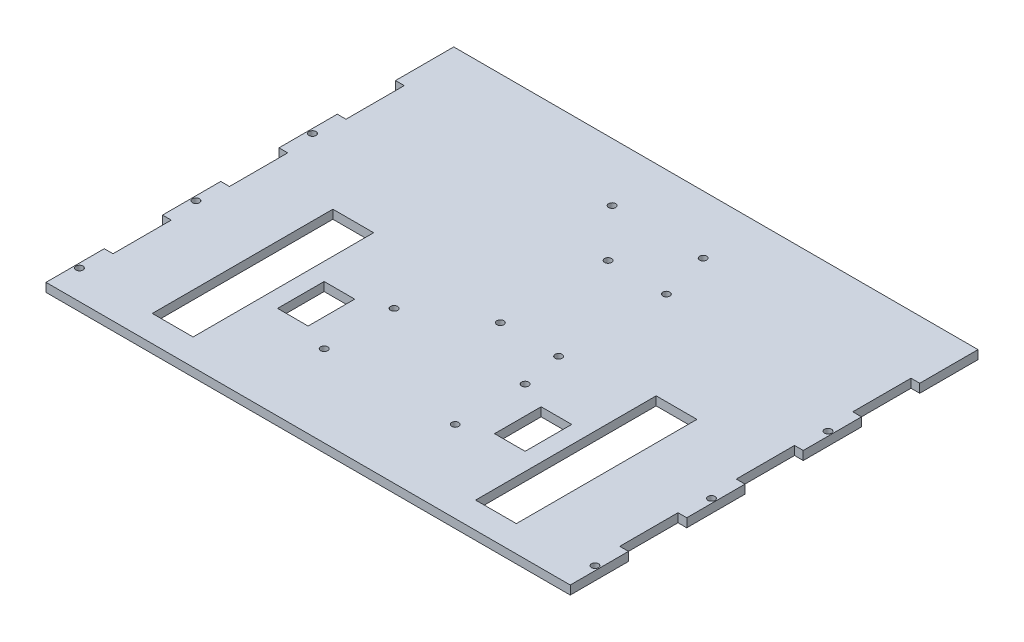
SolidWorks part; units mm, degrees
material "Acrylic (Medium-high impact)"
ref_plane "Front" through (0, 0, 0) normal (0, 0, 1) x (1, 0, 0)
ref_plane "Top" through (0, 0, 0) normal (0, 1, 0) x (1, 0, 0)
ref_plane "Right" through (0, 0, 0) normal (1, 0, 0) x (0, 0, -1)
sketch "Sketch1" plane through (0, 0, 0) normal (0, 1, 0) x (1, 0, 0)
  line L0 (-110.49, 0) -> (110.49, 0) construction
  line L5 (-114.3, -88.9) -> (114.3, -88.9)
  line L7 (-114.3, 88.9) -> (114.3, 88.9)
  line L9 (0, 88.9) -> (0, -88.9) construction
  line L10 (-28.575, -22.86) -> (-28.575, -53.34) construction
  line L11 (-40.64, -27.94) -> (-53.975, -27.94)
  line L12 (-40.64, -27.94) -> (-40.64, -48.26)
  line L13 (-40.64, -48.26) -> (-53.975, -48.26)
  line L14 (-53.975, -27.94) -> (-53.975, -48.26)
  line L15 (-114.3, -38.1) -> (114.3, -38.1) construction
  line L16 (61.595, 1.27) -> (61.595, -77.47)
  line L17 (-79.375, 1.27) -> (-61.595, 1.27)
  line L18 (-79.375, 1.27) -> (-79.375, -77.47)
  line L19 (-79.375, -77.47) -> (-61.595, -77.47)
  line L20 (-61.595, 1.27) -> (-61.595, -77.47)
  line L21 (79.375, -77.47) -> (61.595, -77.47)
  line L22 (79.375, 1.27) -> (79.375, -77.47)
  line L23 (79.375, 1.27) -> (61.595, 1.27)
  line L24 (53.975, -27.94) -> (53.975, -48.26)
  line L25 (40.64, -48.26) -> (53.975, -48.26)
  line L26 (40.64, -27.94) -> (40.64, -48.26)
  line L27 (40.64, -27.94) -> (53.975, -27.94)
  line L28 (114.3, 63.5) -> (110.49, 63.5)
  line L29 (110.49, 63.5) -> (110.49, 38.1)
  line L30 (110.49, 38.1) -> (114.3, 38.1)
  line L31 (114.3, 63.5) -> (114.3, 88.9)
  line L32 (114.3, 12.7) -> (114.3, 38.1)
  line L33 (114.3, 12.7) -> (110.49, 12.7)
  line L34 (110.49, 12.7) -> (110.49, -12.7)
  line L35 (110.49, -12.7) -> (114.3, -12.7)
  line L36 (114.3, -38.1) -> (114.3, -12.7)
  line L37 (114.3, -38.1) -> (110.49, -38.1)
  line L38 (110.49, -38.1) -> (110.49, -63.5)
  line L39 (110.49, -63.5) -> (114.3, -63.5)
  line L40 (114.3, -63.5) -> (114.3, -88.9)
  line L41 (-114.3, 63.5) -> (-114.3, 88.9)
  line L42 (-114.3, -63.5) -> (-114.3, -88.9)
  line L43 (-110.49, -63.5) -> (-114.3, -63.5)
  line L44 (-110.49, -38.1) -> (-110.49, -63.5)
  line L45 (-114.3, -38.1) -> (-110.49, -38.1)
  line L46 (-114.3, -38.1) -> (-114.3, -12.7)
  line L47 (-110.49, -12.7) -> (-114.3, -12.7)
  line L48 (-110.49, 12.7) -> (-110.49, -12.7)
  line L49 (-114.3, 12.7) -> (-110.49, 12.7)
  line L50 (-114.3, 12.7) -> (-114.3, 38.1)
  line L51 (-110.49, 38.1) -> (-114.3, 38.1)
  line L52 (-110.49, 63.5) -> (-110.49, 38.1)
  line L53 (-114.3, 63.5) -> (-110.49, 63.5)
  line L54 (114.3, -76.2) -> (-114.3, -76.2) construction
  line L55 (112.395, -63.5) -> (112.395, -88.9) construction
  line L56 (112.395, -76.2) -> (-112.395, -76.2) construction
  line L57 (112.395, -76.2) -> (112.395, -25.4) construction
  circle A0 centre (-28.575, -22.86) radius 1.524
  circle A1 centre (-28.575, -53.34) radius 1.524
  circle A2 centre (28.575, -53.34) radius 1.524
  circle A3 centre (28.575, -22.86) radius 1.524
  circle A4 centre (0, 41.91) radius 1.524
  circle A5 centre (0, -5.08) radius 1.524
  circle A6 centre (25.4, -5.08) radius 1.524
  circle A7 centre (25.4, 41.91) radius 1.524
  circle A11 centre (112.395, -76.2) radius 1.524
  circle A16 centre (-112.395, -76.2) radius 1.524
  circle A17 centre (-112.395, -25.4) radius 1.524
  circle A18 centre (-112.395, 25.4) radius 1.524
  circle A19 centre (112.395, -25.4) radius 1.524
  circle A20 centre (112.395, 25.4) radius 1.524
  circle A21 centre (-19.8501, 63.5) radius 1.524
  circle A22 centre (19.8501, 63.5) radius 1.524
  point P0 (0, 0)
  point P11 (0, 0)
  point P17 (-61.595, -38.1)
  point P18 (-28.575, -38.1)
  point P20 (-40.64, -38.1)
  point P73 (-110.49, 0)
  dimension "D4" = 3.048
  dimension "D13" = 3.048
  dimension "D22" = 3.048
  dimension "D1" = 228.6
  dimension "D2" = 177.8
  dimension "D3" = 30.48
  dimension "D5" = 20.32
  dimension "D6" = 13.335
  dimension "D7" = 78.74
  dimension "D8" = 17.78
  dimension "D9" = 25.4
  dimension "D10" = 50.8
  dimension "D11" = 50.8
  dimension "D12" = 57.15
  dimension "D14" = 46.99
  dimension "D15" = 25.4
  dimension "D16" = 3
  dimension "D17" = 46.99
  dimension "D18" = 25.4
  dimension "D19" = 3.81
  dimension "D20" = 25.4
  dimension "D21" = 114.3
  dimension "D23" = 2
  dimension "D25" = 1.905
  dimension "D26" = 50.8
  dimension "D27" = 90
  dimension "D28" = 39.7002
  dimension "D29" = 25.4
  dimension "D24" = 3
extrude "Boss-Extrude1" add sketch "Sketch1" along normal blind 3.81
